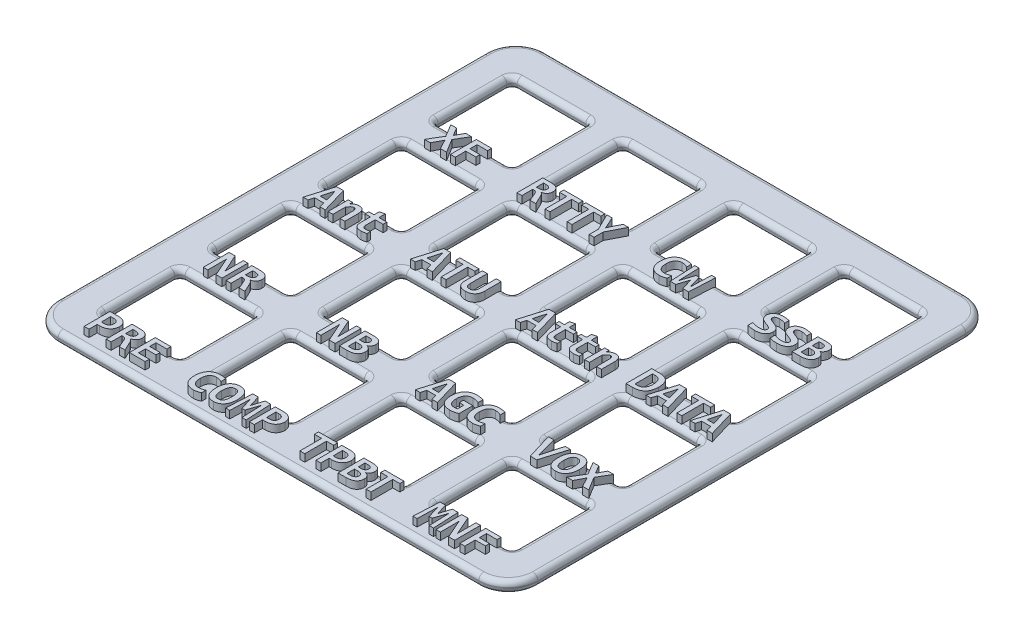
SolidWorks part; units mm, degrees
ref_plane "Front" through (0, 0, 0) normal (0, 0, 1) x (1, 0, 0)
ref_plane "Top" through (0, 0, 0) normal (0, 1, 0) x (1, 0, 0)
ref_plane "Right" through (0, 0, 0) normal (1, 0, 0) x (0, 0, -1)
sketch "Sketch1" plane through (0, 0, 0) normal (0, 1, 0) x (1, 0, 0)
  line L1 (-14.8807, -14.5355) -> (42.1193, -14.5355)
  line L2 (-18.8807, -18.5355) -> (-18.8807, -76.5355)
  line L3 (-14.8807, -80.5355) -> (42.1193, -80.5355)
  line L4 (46.1193, -18.5355) -> (46.1193, -76.5355)
  arc A0 (-14.8807, -14.5355) -> (-18.8807, -18.5355) centre (-14.8807, -18.5355) ccw
  arc A1 (46.1193, -18.5355) -> (42.1193, -14.5355) centre (42.1193, -18.5355) ccw
  arc A2 (42.1193, -80.5355) -> (46.1193, -76.5355) centre (42.1193, -76.5355) ccw
  arc A3 (-18.8807, -76.5355) -> (-14.8807, -80.5355) centre (-14.8807, -76.5355) ccw
  dimension "D1" = 65
  dimension "D2" = 66
extrude "main" add sketch "Sketch1" along normal blind 1.5
sketch "Sketch2" plane through (0, 1.5, 0) normal (0, 1, 0) x (1, 0, 0)
  line L0 (42.1193, -14.5355) -> (-14.8807, -14.5355) construction
  line L1 (-14.2307, -19.6855) -> (-3.5307, -19.6855)
  line L2 (-14.2307, -19.6855) -> (-14.2307, -30.3855)
  line L3 (-14.2307, -30.3855) -> (-3.5307, -30.3855)
  line L4 (-3.5307, -19.6855) -> (-3.5307, -30.3855)
  line L5 (-18.8807, -18.5355) -> (-18.8807, -76.5355) construction
  point P4 (-8.8807, -19.6855)
  dimension "D1" = 5.15
  dimension "D2" = 4.65
  dimension "D3" = 10.7
  dimension "D4" = 10.7
extrude "button hole 1" cut sketch "Sketch2" against normal through all
fillet "button fillet" radius 0.7 12 edges at (-8.8807, 0, 30.3855) (-8.8807, 1.5, 30.3855) (-8.8807, 0, 19.6855) (-8.8807, 1.5, 19.6855) (-3.5307, 0.75, 30.3855) (-3.5307, 0, 25.0355) (-3.5307, 0.75, 19.6855) (-3.5307, 1.5, 25.0355) (-14.2307, 0.75, 19.6855) (-14.2307, 0, 25.0355) (-14.2307, 0.75, 30.3855) (-14.2307, 1.5, 25.0355)
pattern_linear "buttons by 16" count 4 spacing 15 along (1, 0, 0) count 4 spacing 15 along (0, 0, 1) of "button fillet", "button hole 1"
fillet "outer edge fillet" radius 0.7 16 edges at (13.6193, 1.5, 14.5355) (13.6193, 0, 14.5355) (46.1193, 1.5, 47.5355) (46.1193, 0, 47.5355) (13.6193, 1.5, 80.5355) (13.6193, 0, 80.5355) (-18.8807, 1.5, 47.5355) (-18.8807, 0, 47.5355) (44.9477, 1.5, 15.7071) (44.9477, 1.5, 79.364) (-17.7092, 1.5, 79.364) (-17.7092, 1.5, 15.7071) (44.9477, 0, 15.7071) (44.9477, 0, 79.364) (-17.7092, 0, 79.364) (-17.7092, 0, 15.7071)
sketch "Lettering" plane through (0, 0, 0) normal (0, 1, 0) x (1, 0, 0)
  line L0 (45.4193, -49.1355) -> (-18.1807, -49.1355) construction
  line L1 (45.4783, -79.1355) -> (-16.5217, -79.1355) construction
  line L2 (45.4193, -76.5355) -> (45.4193, -18.5355) construction
  line L3 (-18.1807, -18.5355) -> (-18.1807, -76.5355) construction
  line L5 (45.4193, -64.1355) -> (-18.1807, -64.1355) construction
  line L6 (45.4193, -76.5355) -> (45.4193, -18.5355) construction
  line L7 (-18.1807, -18.5355) -> (-18.1807, -76.5355) construction
  line L8 (45.4193, -34.1355) -> (-18.1807, -34.1355) construction
  line L11 (-14.8807, -80.5355) -> (42.1193, -80.5355) construction
  text T0 "SSB" font "Consolas" height 3.5
  text T1 "CW" font "Consolas" height 3.5
  text T2 "RTTY" font "Consolas" height 3.5
  text T3 "XF" font "Consolas" height 3.5
  text T4 "VOX" font "Consolas" height 3.5
  text T5 "AGC" font "Consolas" height 3.5
  text T6 "MNF" font "Consolas" height 3.5
  text T7 "Attn" font "Consolas" height 3.5
  text T8 "Ant" font "Consolas" height 3.5
  text T9 "TPBT" font "Consolas" height 3.5
  text T10 "COMP" font "Consolas" height 3.5
  text T11 "PRE" font "Consolas" height 3.5
  text T12 "DATA" font "Consolas" height 3.5
  text T13 "NB" font "Consolas" height 3.5
  text T14 "ATU" font "Consolas" height 3.5
  text T15 "NR" font "Consolas" height 3.5
  dimension "D1" = 46.4
  dimension "D2" = 16.4
  dimension "D3" = 1.4
  dimension "D4" = 31.4
extrude "lettering boss" add sketch "Lettering" along normal blind 2.5
